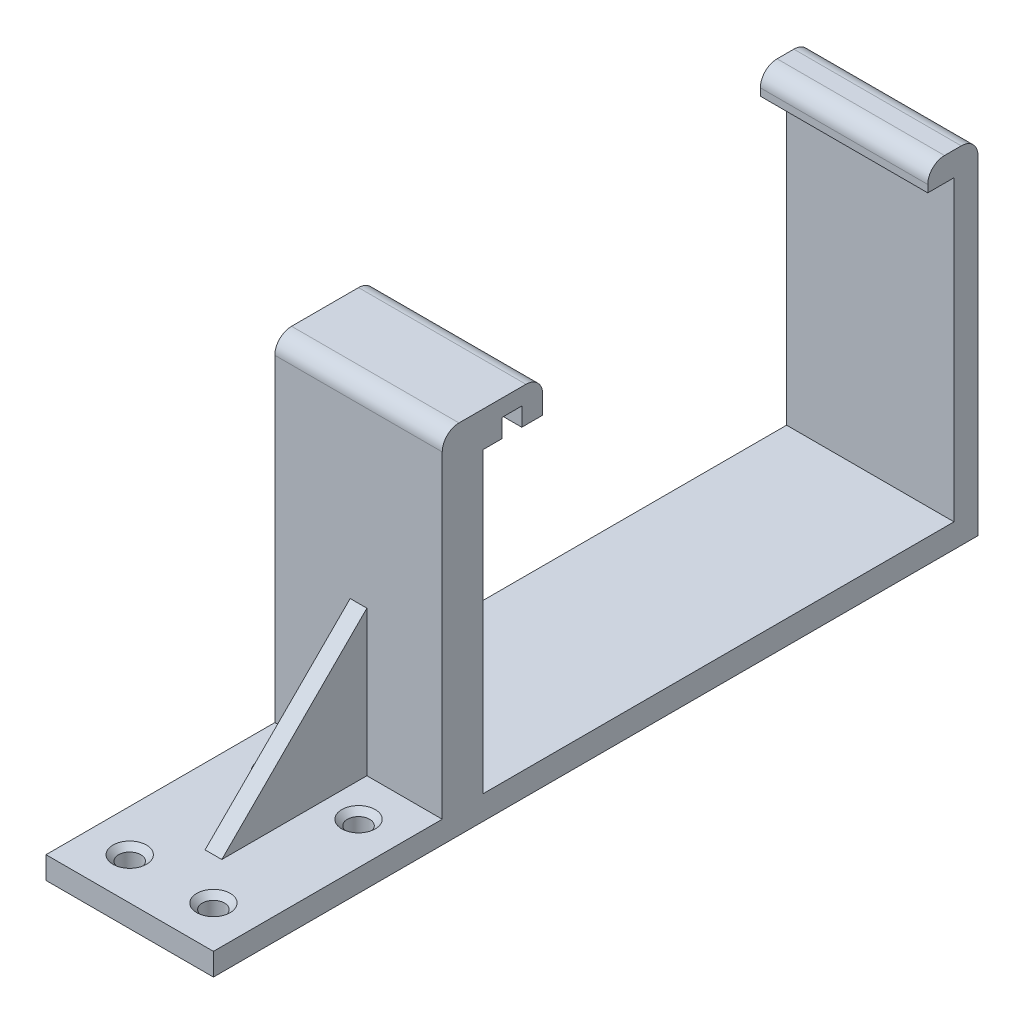
SolidWorks part; units mm, degrees
ref_plane "Front Plane" through (0, 0, 0) normal (0, 0, 1) x (1, 0, 0)
ref_plane "Top Plane" through (0, 0, 0) normal (0, 1, 0) x (1, 0, 0)
ref_plane "Right Plane" through (0, 0, 0) normal (1, 0, 0) x (0, 0, -1)
sketch "Sketch1" plane through (0, 0, 0) normal (0, 1, 0) x (1, 0, 0)
  line L1 (0, 0) -> (30, 0)
  line L2 (0, 0) -> (0, 45)
  line L3 (0, 45) -> (30, 45)
  line L4 (30, 0) -> (30, 45)
  dimension "D1" = 45
  dimension "D2" = 30
extrude "Boss-Extrude1" add sketch "Sketch1" along normal blind 4
sketch "Sketch2" plane through (0, 4, 0) normal (0, 1, 0) x (1, 0, 0)
  line L0 (0, 45) -> (0, 0) construction
  line L1 (30, 45) -> (0, 45)
  line L2 (30, 45) -> (30, 41)
  line L3 (30, 41) -> (0, 41)
  line L4 (0, 45) -> (0, 41)
  dimension "D1" = 4
extrude "Boss-Extrude2" add sketch "Sketch2" along normal blind 58
sketch "Sketch7" plane through (0, 4, 0) normal (0, 1, 0) x (1, 0, 0)
  line L0 (15, 41) -> (15, 0) construction
  line L1 (0, 41) -> (30, 41) construction
  line L2 (0, 0) -> (30, 0) construction
  line L3 (13.5, 0) -> (13.5, 41)
  line L4 (13.5, 0) -> (16.5, 0)
  line L5 (13.5, 41) -> (16.5, 41)
  line L6 (16.5, 0) -> (16.5, 41)
  line L7 (13.5, 0) -> (16.5, 41) construction
  line L8 (13.5, 41) -> (16.5, 0) construction
  point P7 (15, 20.5)
  dimension "D1" = 3
extrude "Boss-Extrude3" add sketch "Sketch7" along normal blind 41
sketch "Sketch8" plane through (16.5, 0, 0) normal (1, 0, 0) x (0, 0, -1)
  line L1 (41, 45) -> (0, 45)
  line L2 (0, 45) -> (0, 4)
  line L3 (0, 4) -> (15, 4)
  line L4 (0, 4) -> (41, 4) construction
  line L5 (15, 4) -> (41, 30)
  line L6 (41, 45) -> (41, 4) construction
  line L7 (41, 30) -> (41, 45)
  dimension "D1" = 15
  dimension "D2" = 36.7696
extrude "Cut-Extrude1" cut sketch "Sketch8" against normal up to surface (3 mm away) up to face at (13.5, 24.5, -20.5)
sketch "Sketch10" plane through (0, 4, 0) normal (0, 1, 0) x (1, 0, 0)
  line L0 (15, 15) -> (15, 0) construction
  line L1 (13.5, 15) -> (16.5, 15) construction
  line L2 (0, 0) -> (30, 0) construction
  line L3 (15, 7.5) -> (30, 7.5) construction
  line L4 (0, 20.5) -> (30, 20.5) construction
  line L6 (30, 0) -> (30, 41) construction
  line L7 (15, 7.5) -> (0, 7.5) construction
  line L8 (0, 41) -> (0, 0) construction
  circle A0 centre (7.5, 7.5) radius 2
  circle A1 centre (22.5, 7.5) radius 2
  circle A2 centre (22.5, 33.5) radius 2
  circle A3 centre (7.5, 33.5) radius 2
  point P10 (7.5, 7.5)
  point P12 (22.5, 7.5)
  point P30 (22.5, 33.5)
  point P31 (7.5, 33.5)
  dimension "D1" = 4
  dimension "D2" = 4
extrude "Cut-Extrude2" cut sketch "Sketch10" against normal up to surface (4 mm away) up to face at (15, 0, -22.5)
chamfer "Chamfer1" distance 1 angle 45 4 edges at (22.5, 4, -5.5) (7.5, 4, -5.5) (7.5, 4, -35.5) (22.5, 4, -35.5)
ref_plane "Plane3" through (15, 0, 0) normal (1, 0, 0) x (0, 0, -1)
sketch "Sketch11" plane through (15, 0, 0) normal (1, 0, 0) x (0, 0, -1)
  line L0 (45, 0) -> (137, 0)
  line L2 (137, 0) -> (137, 62)
  line L3 (137, 62) -> (128, 62)
  line L4 (128, 62) -> (128, 58)
  line L5 (128, 58) -> (133, 58)
  line L6 (133, 58) -> (133, 4)
  line L7 (133, 4) -> (49, 4)
  line L8 (49, 4) -> (49, 58)
  line L9 (49, 58) -> (59, 58)
  line L10 (59, 58) -> (59, 62)
  line L11 (59, 62) -> (45, 62)
  line L13 (45, 62) -> (45, 0)
  dimension "D1" = 4
  dimension "D2" = 54
  dimension "D3" = 4
  dimension "D4" = 4
  dimension "D5" = 4
  dimension "D6" = 84
  dimension "D7" = 5
  dimension "D8" = 10
extrude "Boss-Extrude4" add sketch "Sketch11" against normal mid plane 30
sketch "Sketch12" plane through (0, 0, 0) normal (-1, 0, 0) x (0, 0, 1)
  line L0 (-55.25, 58) -> (-55.25, 61)
  line L5 (-55.25, 59.5) -> (-59, 59.5) construction
  line L11 (-55.25, 61) -> (-51.75, 61)
  line L12 (-51.75, 58) -> (-51.75, 61)
  line L13 (-55.25, 58) -> (-51.75, 58)
  line L14 (-59, 58) -> (-59, 62) construction
  line L16 (-49, 58) -> (-59, 58) construction
  line L18 (-49, 59.5) -> (-49, 58) construction
  line L19 (-49, 4) -> (-49, 58) construction
  dimension "D1" = 3
  dimension "D2" = 3.5
  dimension "D3" = 3.75
extrude "Cut-Extrude3" cut sketch "Sketch12" against normal up to surface (30 mm away) up to face at (30, 35.4286, -78.1429)
sketch "Sketch13" plane through (30, 0, 0) normal (1, 0, 0) x (0, 0, -1)
  line L0 (59, 58) -> (59, 62) construction
  line L1 (41, 62) -> (59, 62)
  line L2 (41, 62) -> (41, 64)
  line L3 (41, 64) -> (59, 64)
  line L4 (59, 62) -> (59, 64)
  dimension "D1" = 2
extrude "Boss-Extrude5" add sketch "Sketch13" against normal up to surface (30 mm away) up to face at (0, 40.7778, -72.6667)
sketch "Sketch14" plane through (0, 0, 0) normal (-1, 0, 0) x (0, 0, 1)
  line L0 (-133, 4) -> (-49, 4) construction
  line L1 (-49, 58) -> (-48, 58)
  line L2 (-49, 58) -> (-49, 4)
  line L3 (-49, 4) -> (-48, 4)
  line L4 (-48, 58) -> (-48, 4)
  dimension "D1" = 1
extrude "Cut-Extrude4" cut sketch "Sketch14" against normal up to surface (30 mm away) up to face at (30, 41, -72.6667)
sketch "Sketch15" plane through (0, 0, 0) normal (-1, 0, 0) x (0, 0, 1)
  line L56 (-59, 58) -> (-59, 64) construction
  line L57 (-59, 57.7) -> (-59, 58)
  line L58 (-59, 58) -> (-55.25, 58)
  line L59 (-55.25, 58) -> (-55.25, 57.7)
  line L60 (-51.75, 58) -> (-51.75, 57.7)
  line L61 (-48.3, 57.7) -> (-51.75, 57.7)
  line L62 (-48.3, 4.3) -> (-48.3, 57.7)
  line L63 (-132.7, 4.3) -> (-48.3, 4.3)
  line L64 (-132.7, 57.7) -> (-132.7, 4.3)
  line L65 (-128, 57.7) -> (-132.7, 57.7)
  line L66 (-48.3, 57.7) -> (-51.75, 57.7)
  line L67 (-48.3, 4.3) -> (-48.3, 57.7)
  line L68 (-132.7, 4.3) -> (-48.3, 4.3)
  line L69 (-132.7, 57.7) -> (-132.7, 4.3)
  line L70 (-128, 57.7) -> (-132.7, 57.7)
  line L71 (-55.25, 57.7) -> (-59, 57.7)
  line L72 (-51.75, 58) -> (-48, 58)
  line L73 (-48, 58) -> (-48, 4)
  line L74 (-48, 4) -> (-133, 4)
  line L75 (-133, 4) -> (-133, 58)
  line L76 (-133, 58) -> (-128, 58)
  line L77 (-128, 58) -> (-128, 57.7)
  dimension "D1" = 0.3
extrude "Boss-Extrude6" add sketch "Sketch15" against normal up to surface (30 mm away) up to face at (30, 41, -72.5556)
fillet "Fillet1" radius 3 4 edges at (15, 64, -41) (15, 64, -59) (15, 62, -128) (15, 62, -137)
